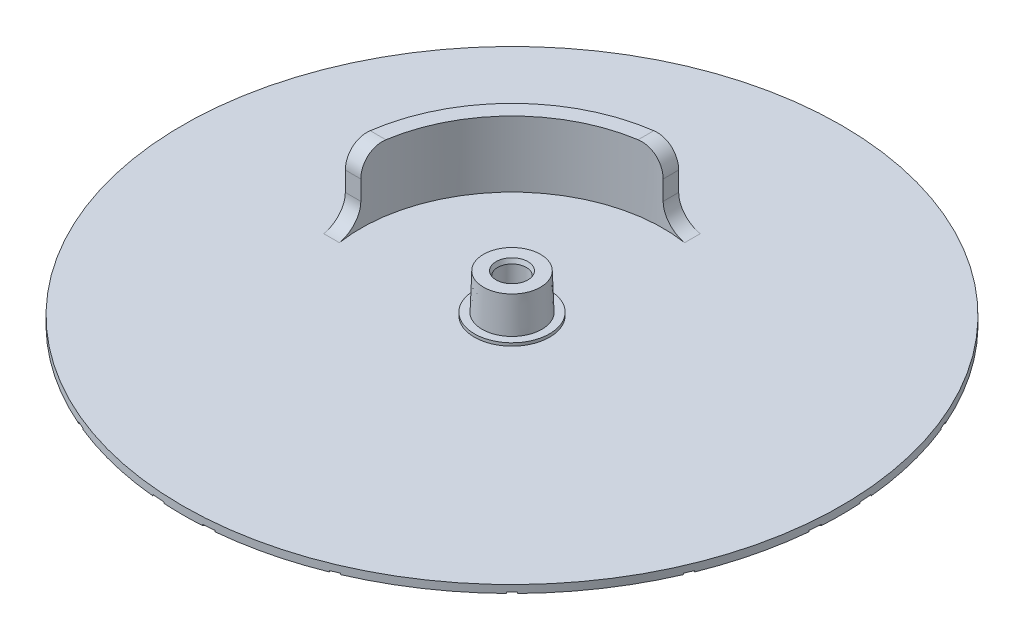
SolidWorks part; units mm, degrees
ref_plane "Front Plane" through (0, 0, 0) normal (0, 0, 1) x (1, 0, 0)
ref_plane "Top Plane" through (0, 0, 0) normal (0, 1, 0) x (1, 0, 0)
ref_plane "Right Plane" through (0, 0, 0) normal (1, 0, 0) x (0, 0, -1)
sketch "Sketch1" plane through (0, 0, 0) normal (0, 1, 0) x (1, 0, 0)
  circle A0 centre (0, 0) radius 21.5
  circle A1 centre (0, 0) radius 2.15
  dimension "D1" = 43
extrude "Boss-Extrude1" add sketch "Sketch1" along normal blind 1
sketch "Sketch2" plane through (0, 1, 0) normal (0, 1, 0) x (1, 0, 0)
  line L0 (0, 19.5) -> (0, 21.5)
  line L1 (-19.5, 0) -> (-21.5, 0)
  arc A0 (0, 21.5) -> (-21.5, 0) centre (0, 0) ccw
  arc A1 (0, 19.5) -> (-19.5, 0) centre (0, 0) ccw
  circle A2 centre (0, 0) radius 21.5 construction
  dimension "D1" = 2
extrude "Boss-Extrude2" add sketch "Sketch2" along normal blind 8.5
sketch "Sketch3" plane through (0, 1, 0) normal (0, 1, 0) x (1, 0, 0)
  circle A0 centre (0, 0) radius 3.85
  dimension "D1" = 7.7
extrude "Boss-Extrude3" add sketch "Sketch3" along normal blind 5
chamfer "Chamfer1" distance 5 angle 2 1 edges at (0, 6, 3.85) first distance on face at (0, 6, 3.85)
sketch "Sketch4" plane through (0, 6, 0) normal (0, 1, 0) x (1, 0, 0)
  circle A0 centre (0, 0) radius 1.85
  dimension "D1" = 3.7
extrude "Cut-Extrude1" cut sketch "Sketch4" against normal blind 9
chamfer "Chamfer2" distance 0.2 angle 70 1 edges at (0, 6, 1.85) first distance on face at (0, 6, 1.85)
sketch "Sketch5" plane through (0, 1, 0) normal (0, 1, 0) x (1, 0, 0)
  circle A0 centre (0, 0) radius 3.85
  circle A1 centre (0, 0) radius 4.85
  dimension "D1" = 1
extrude "Boss-Extrude4" add sketch "Sketch5" along normal blind 0.38
fillet "Fillet1" radius 3 4 edges at (-20.5, 9.5, 0) (-20.5, 1, 0) (0, 9.5, -20.5) (0, 1, -20.5)
sketch "Sketch6" plane through (0, 1, 0) normal (0, 1, 0) x (1, 0, 0)
  circle A0 centre (0, 0) radius 42.5
  circle A1 centre (0, 0) radius 2.15
  dimension "D1" = 85
extrude "Boss-Extrude6" add sketch "Sketch6" against normal up to surface (1 mm away) up to face at (0, 0, 21.5)
sketch "Sketch8" plane through (0, 0, 0) normal (0, -1, 0) x (1, 0, 0)
  line L0 (0, 0) -> (-37.1856, 37.1856) construction
  line L1 (0, 0) -> (-58.8083, 0) construction
  line L2 (62.9923, -63.6994) -> (-63.6994, 62.9923)
  line L3 (62.9923, -63.6994) -> (63.6994, -62.9923)
  line L4 (-63.6994, 62.9923) -> (-62.9923, 63.6994)
  line L5 (63.6994, -62.9923) -> (-62.9923, 63.6994)
  line L6 (62.9923, -63.6994) -> (-62.9923, 63.6994) construction
  line L7 (-63.6994, 62.9923) -> (63.6994, -62.9923) construction
  line L8 (85.7999, -63.6994) -> (-40.8919, 62.9923)
  line L9 (85.7999, -63.6994) -> (86.507, -62.9923)
  line L10 (86.507, -62.9923) -> (-40.1848, 63.6994)
  line L11 (-40.8919, 62.9923) -> (-40.1848, 63.6994)
  line L12 (108.6074, -63.6994) -> (-18.0844, 62.9923)
  line L13 (108.6074, -63.6994) -> (109.3145, -62.9923)
  line L14 (109.3145, -62.9923) -> (-17.3773, 63.6994)
  line L15 (-18.0844, 62.9923) -> (-17.3773, 63.6994)
  line L28 (40.1848, -63.6994) -> (-86.507, 62.9923)
  line L29 (40.1848, -63.6994) -> (40.8919, -62.9923)
  line L30 (40.8919, -62.9923) -> (-85.7999, 63.6994)
  line L31 (-86.507, 62.9923) -> (-85.7999, 63.6994)
  line L32 (17.3773, -63.6994) -> (-109.3145, 62.9923)
  line L33 (17.3773, -63.6994) -> (18.0844, -62.9923)
  line L34 (18.0844, -62.9923) -> (-108.6074, 63.6994)
  line L35 (-109.3145, 62.9923) -> (-108.6074, 63.6994)
  line L40 (40.1848, -63.6994) -> (17.3773, -63.6994) construction
  line L42 (109.3145, -62.9923) -> (86.507, -62.9923) construction
  point P2 (-63.3459, 63.3459)
  point P5 (15.7758, -63.1345)
  point P19 (12.7289, -63.6994)
  point P20 (37.8606, -64.3415)
  point P21 (79.3678, -63.3459)
  dimension "D1" = 45
  dimension "D2" = 1
  dimension "D3" = 3
  dimension "D4" = 3
extrude "Cut-Extrude2" cut sketch "Sketch8" against normal blind 0.16
pattern_circular "CirPattern1" count 2 every 90 about axis through (0, 6, 0) along (0, -1, 0) of "Cut-Extrude2"
equation "\"D3@Sketch8\"=\"D4@Sketch8\""
